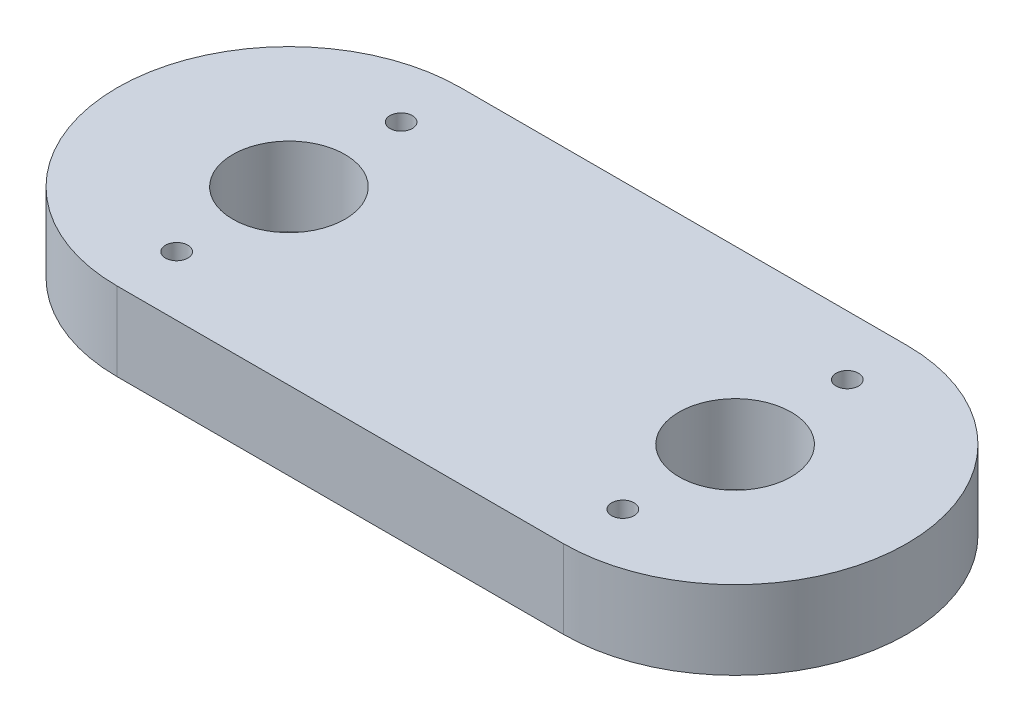
SolidWorks part; units mm, degrees
ref_plane "Front Plane" through (0, 0, 0) normal (0, 0, 1) x (1, 0, 0)
ref_plane "Top Plane" through (0, 0, 0) normal (0, 1, 0) x (1, 0, 0)
ref_plane "Right Plane" through (0, 0, 0) normal (1, 0, 0) x (0, 0, -1)
sketch "Sketch1" plane through (0, 0, 0) normal (0, 1, 0) x (1, 0, 0)
  line L0 (-31.9723, 0) -> (7.786, 0)
  line L1 (7.786, -30.6106) -> (-31.9723, -30.6106)
  arc A0 (7.786, 0) -> (7.786, -30.6106) centre (7.786, -15.3053) cw
  arc A1 (-31.9723, -30.6106) -> (-31.9723, 0) centre (-31.9723, -15.3053) cw
  dimension "D1" = 39.7583
  dimension "D2" = 30.6106
extrude "Boss-Extrude1" add sketch "Sketch1" along normal blind 7
sketch "Sketch2" plane through (0, 7, 0) normal (0, 1, 0) x (1, 0, 0)
  line L0 (-12.0932, -54.7734) -> (-12.0932, 0) construction
  line L1 (-31.9723, 0) -> (-31.9723, -30.6106) construction
  line L2 (-54.6054, -15.3053) -> (-12.0932, -15.3053) construction
  line L3 (7.786, 0) -> (-31.9723, 0) construction
  circle A0 centre (-31.9723, -15.3053) radius 5
  circle A1 centre (-31.9723, -5.3053) radius 1
  circle A2 centre (-31.9723, -25.3053) radius 1
  circle A3 centre (7.786, -5.3053) radius 1
  circle A4 centre (7.786, -15.3053) radius 5
  circle A5 centre (7.786, -25.3053) radius 1
  point P23 (-12.0932, 0)
  dimension "D1" = 10
  dimension "D2" = 2
  dimension "D3" = 10
extrude "Cut-Extrude1" cut sketch "Sketch2" against normal through all
